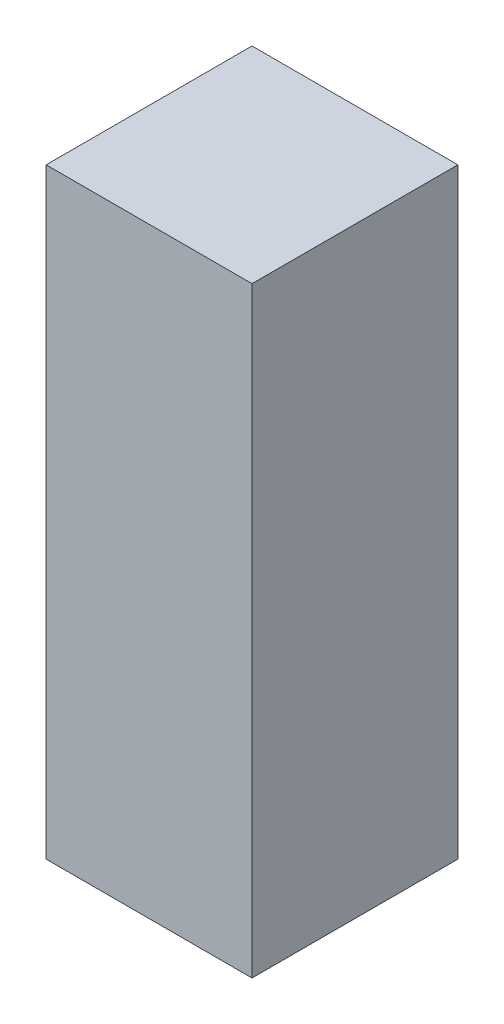
SolidWorks part; units mm, degrees
material "Beryllium"
ref_plane "Front Plane" through (0, 0, 0) normal (0, 0, 1) x (1, 0, 0)
ref_plane "Top Plane" through (0, 0, 0) normal (0, 1, 0) x (1, 0, 0)
ref_plane "Right Plane" through (0, 0, 0) normal (1, 0, 0) x (0, 0, -1)
sketch "Sketch1" plane through (0, 0, 0) normal (0, 1, 0) x (1, 0, 0)
  line L1 (-25.5, -25.5) -> (25.5, -25.5)
  line L2 (-25.5, -25.5) -> (-25.5, 25.5)
  line L3 (-25.5, 25.5) -> (25.5, 25.5)
  line L4 (25.5, -25.5) -> (25.5, 25.5)
  line L5 (-25.5, -25.5) -> (25.5, 25.5) construction
  line L6 (-25.5, 25.5) -> (25.5, -25.5) construction
  point P0 (0, 0)
  dimension "D1" = 51
  dimension "D2" = 51
extrude "Boss-Extrude1" add sketch "Sketch1" along normal blind 149
sketch "Sketch2" plane through (0, 0, 0) normal (0, 0, 1) x (1, 0, 0)
  line L0 (-25.5, 149) -> (25.5, 0) construction
  line L1 (-4.2747, 86.9887) -> (4.2747, 62.0113)
  arc A1 (-4.2747, 86.9887) -> (4.2747, 62.0113) centre (0, 74.5) cw
  point P8 (0, 74.5)
  dimension "D1" = 13.2
revolve "Cut-Revolve1" cut sketch "Sketch2" angle 360 about L0 region at (5.3004, 76.3142, 0)
revolve "Revolve2" add sketch "Sketch2<4>" angle 360 about L0
sketch "Sketch2<4>" plane through (0, 0, 0) normal (0, 0, 1) x (1, 0, 0) same geometry as "Sketch2"
